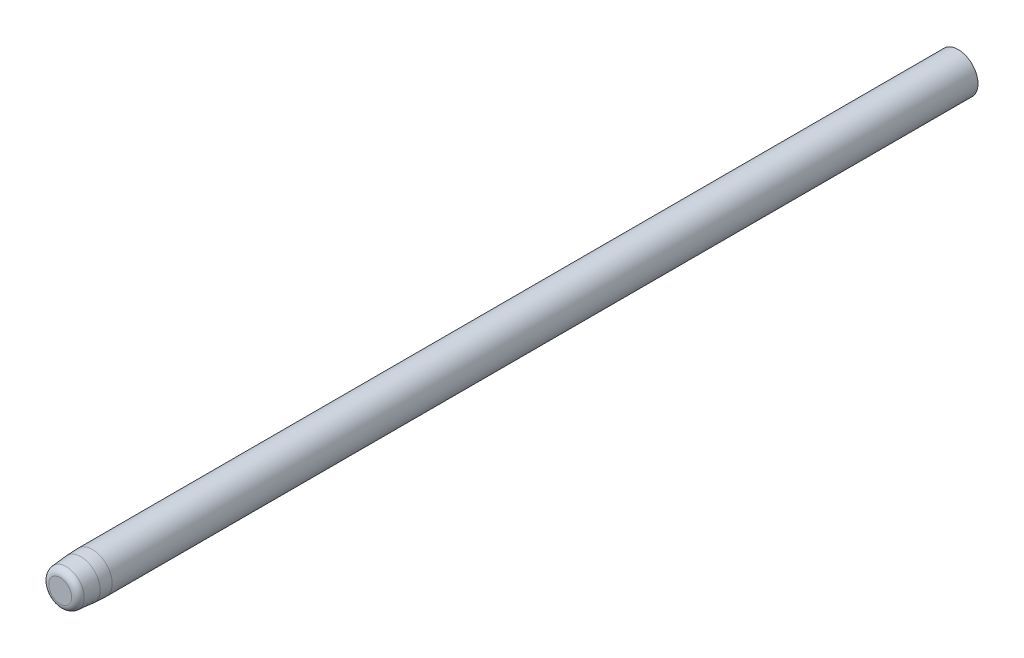
SolidWorks part; units mm, degrees
ref_plane "Front Plane" through (0, 0, 0) normal (0, 0, 1) x (1, 0, 0)
ref_plane "Top Plane" through (0, 0, 0) normal (0, 1, 0) x (1, 0, 0)
ref_plane "Right Plane" through (0, 0, 0) normal (1, 0, 0) x (0, 0, -1)
sketch "Sketch2" plane through (0, 0, 0) normal (0, 0, 1) x (1, 0, 0)
  circle A0 centre (0, 0) radius 1.905
  dimension "D1" = 3.81
extrude "Boss-Extrude1" add sketch "Sketch2" along normal blind 86.36
chamfer "Chamfer1" distance 2.54 angle 5 1 edges at (1.905, 0, 86.36) first distance on face at (1.905, 0, 86.36)
fillet "Fillet1" radius 12.7 1 edges at (1.905, 0, 83.82)
fillet "Fillet2" radius 0.635 1 edges at (1.6828, 0, 86.36)
